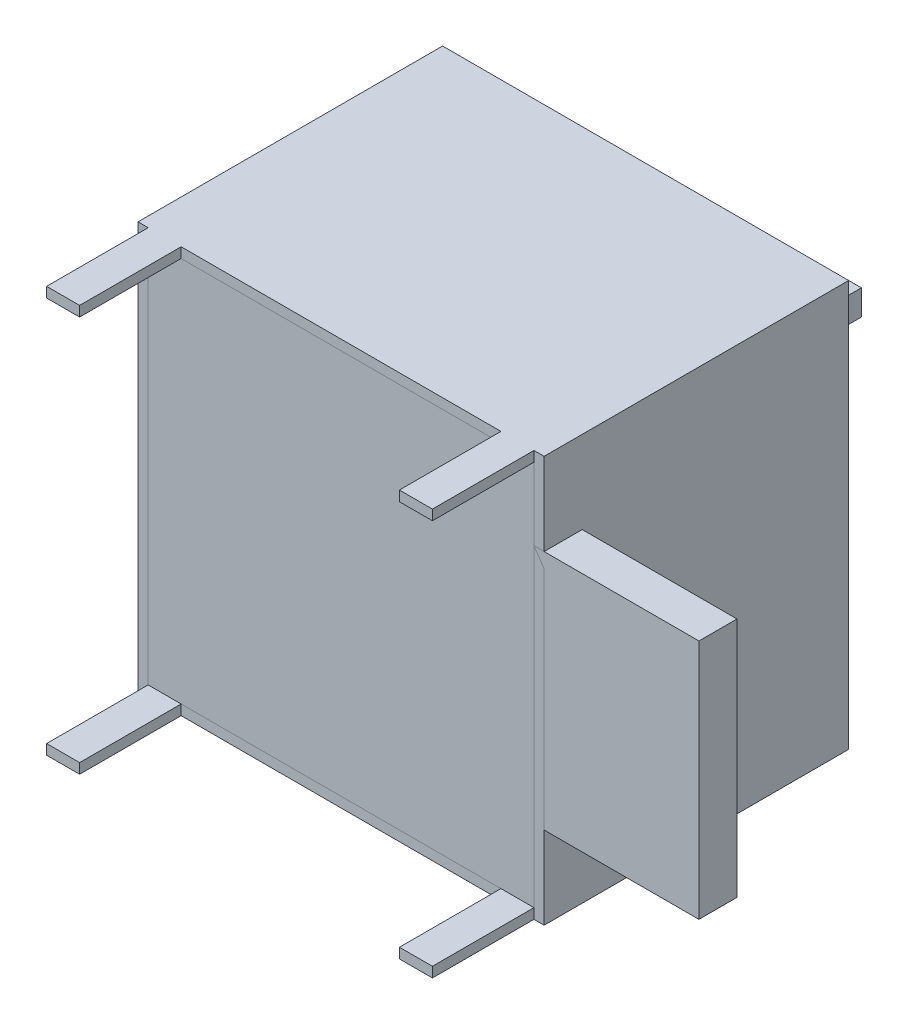
SolidWorks part; units mm, degrees
ref_plane "정면" through (0, 0, 0) normal (0, 0, 1) x (1, 0, 0)
ref_plane "윗면" through (0, 0, 0) normal (0, 1, 0) x (1, 0, 0)
ref_plane "우측면" through (0, 0, 0) normal (1, 0, 0) x (0, 0, -1)
sketch "스케치1" plane through (0, 0, 0) normal (0, 0, 1) x (1, 0, 0)
  line L1 (0, 0) -> (16, 0)
  line L2 (0, 0) -> (0, 16)
  line L3 (0, 16) -> (16, 16)
  line L4 (16, 0) -> (16, 16)
extrude "보스-돌출1" add sketch "스케치1" along normal blind 12
shell "쉘1" thickness 0.4 removed face at (8, 8, 12)
sketch "스케치2" plane through (0, 0, 12) normal (0, 0, 1) x (1, 0, 0)
  line L0 (16, 16) -> (0, 16) construction
  line L1 (0.4, 15.6) -> (1.7, 15.6)
  line L2 (0.4, 15.6) -> (0.4, 16)
  line L3 (0.4, 16) -> (1.7, 16)
  line L4 (1.7, 15.6) -> (1.7, 16)
extrude "보스-돌출2" add sketch "스케치2" along normal blind 4
ref_plane "평면1" through (8, 0, 0) normal (1, 0, 0) x (0, 0, -1)
ref_plane "평면2" through (0, 8, 0) normal (0, 1, 0) x (1, 0, 0)
mirror "대칭 복사1" about plane through (8, 0, 0) normal (1, 0, 0) of "보스-돌출2"
mirror "대칭 복사2" about plane through (0, 8, 0) normal (0, 1, 0) of "대칭 복사1"
sketch "스케치3" plane through (0, 0, 12) normal (0, 0, 1) x (1, 0, 0)
  line L0 (15.6, 15.6) -> (0.4, 15.6) construction
  line L1 (0.4, 15.6) -> (15.6, 15.6)
  line L2 (0.4, 15.6) -> (0.4, 0.4)
  line L3 (0.4, 0.4) -> (15.6, 0.4)
  line L4 (15.6, 15.6) -> (15.6, 12.75)
  line L5 (0.4, 15.6) -> (0.4, 0.4) construction
  line L8 (15.6, 12.75) -> (22.1, 12.75)
  line L10 (15.6, 3.25) -> (22.1, 3.25)
  line L11 (22.1, 12.75) -> (22.1, 3.25)
  line L12 (15.6, 3.25) -> (15.6, 0.4)
  point P12 (15.6, 8)
  dimension "D1" = 6.5
extrude "보스-돌출3" add sketch "스케치3" against normal blind 1.5 separate body
sketch "스케치4" plane through (0, 0, 0) normal (0, 0, -1) x (-1, 0, 0)
  line L0 (8.8, 8) -> (-8.8, 8) construction
  line L1 (-9, 8.5) -> (-7, 8.5)
  line L2 (-9, 8.5) -> (-9, 7.5)
  line L3 (-9, 7.5) -> (-7, 7.5)
  line L4 (-7, 8.5) -> (-7, 7.5)
  line L5 (-9, 8.5) -> (-7, 7.5) construction
  line L6 (-9, 7.5) -> (-7, 8.5) construction
  line L7 (-8, 6.6) -> (-8, -6.6) construction
  point P0 (-8, 8)
extrude "보스-돌출4" add sketch "스케치4" along normal blind 7.5
ref_axis "기준축1" through (8, 8, 16.8) along (0, 0, -1)
